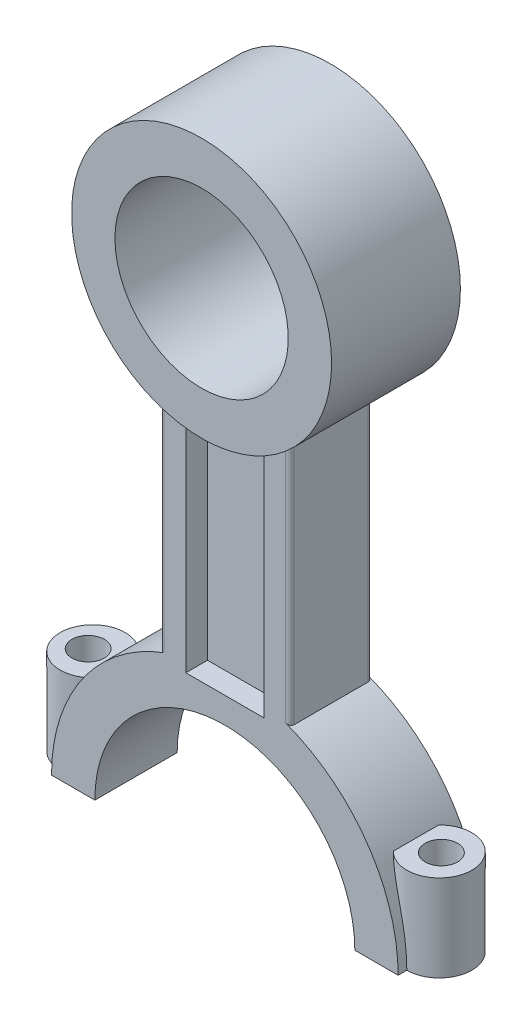
SolidWorks part; units mm, degrees
ref_plane "Front Plane" through (0, 0, 0) normal (0, 0, 1) x (1, 0, 0)
ref_plane "Top Plane" through (0, 0, 0) normal (0, 1, 0) x (1, 0, 0)
ref_plane "Right Plane" through (0, 0, 0) normal (1, 0, 0) x (0, 0, -1)
sketch "Sketch1" plane through (0, 0, 0) normal (0, 0, 1) x (1, 0, 0)
  line L0 (0, 76.2) -> (0, -76.2)
  line L2 (19.05, 59.3995) -> (19.05, -50.9435)
  line L3 (19.05, -50.9435) -> (-19.05, -50.9435)
  line L4 (-19.05, -50.9435) -> (-19.05, 59.3995)
  line L5 (-19.05, 59.3995) -> (19.05, 59.3995)
  line L6 (-50.8, -76.2) -> (-38.1, -76.2)
  line L7 (38.1, -76.2) -> (50.8, -76.2)
  circle A0 centre (0, 76.2) radius 25.4
  circle A1 centre (0, 76.2) radius 38.1
  arc A2 (50.8, -76.2) -> (-50.8, -76.2) centre (0, -76.2) ccw
  arc A3 (38.1, -76.2) -> (-38.1, -76.2) centre (0, -76.2) ccw
  dimension "D3" = 50.8
  dimension "D4" = 76.2
  dimension "D5" = 76.2
  dimension "D6" = 101.6
  dimension "D1" = 152.4
  dimension "D7" = 38.1
  dimension "D8" = 38.1
extrude "Boss-Extrude1" add sketch "Sketch1" along normal mid plane 24.13 contours A2 L0 A1 L4 | A2 L2 A1 L0 | A3 L4 A2 L6 | A3 L0 A2 L4 | A3 L7 A2 L2 | A3 L2 A2 L0 | L2 A1 L4 A0 | L4 A1 L0 A0 | L0 A1 L2 A0 region at (9.8942, 46.7377, 0) region at (-9.8942, 46.7377, 0) region at (-20.0922, 51.302, 0) region at (9.7333, 6.576, 0) region at (-9.7333, 6.576, 0) region at (9.6881, -33.2254, 0) region at (-9.6881, -33.2254, 0) region at (-35.8824, -53.4043, 0) region at (35.8824, -53.4043, 0)
extrude "Boss-Extrude2" add sketch "Sketch1<3>" along normal mid plane 37.75 contours L2 A1 L4 A0 | L4 A1 L0 A0 | L0 A1 L2 A0 region at (9.8942, 46.7377, 0) region at (-9.8942, 46.7377, 0) region at (-20.0922, 51.302, 0)
sketch "Sketch1<3>" plane through (0, 0, 0) normal (0, 0, 1) x (1, 0, 0) same geometry as "Sketch1"
sketch "Sketch4" plane through (0, -76.2, 0) normal (0, -1, 0) x (1, 0, 0)
  line L0 (50.8, 12.065) -> (50.8, -12.065) construction
  circle A0 centre (50.8, 0) radius 9.525
  dimension "D1" = 19.05
extrude "Boss-Extrude5" add sketch "Sketch4" against normal blind 25.4 contours A0
sketch "Sketch5" plane through (0, -76.2, 0) normal (0, -1, 0) x (1, 0, 0)
  circle A0 centre (51.3953, 0) radius 4.76
  dimension "D1" = 9.52
extrude "Cut-Extrude1" cut sketch "Sketch5" against normal blind 25.4
sketch "Sketch6" plane through (0, -76.2, 0) normal (0, -1, 0) x (1, 0, 0)
  line L0 (-50.8, 12.065) -> (-50.8, -12.065) construction
  circle A0 centre (-50.8, 0) radius 9.525
  dimension "D1" = 19.05
extrude "Boss-Extrude6" add sketch "Sketch6" against normal blind 25.4
sketch "Sketch7" plane through (0, -76.2, 0) normal (0, -1, 0) x (1, 0, 0)
  circle A0 centre (-52.1224, 0) radius 4.76
  dimension "D1" = 9.52
extrude "Cut-Extrude2" cut sketch "Sketch7" against normal blind 25.4
sketch "Sketch9" plane through (0, 0, 12.065) normal (0, 0, 1) x (1, 0, 0)
  line L1 (-11.43, 39.8549) -> (11.43, 39.8549) construction
  line L2 (11.43, 39.8549) -> (11.43, -30.5351)
  line L3 (11.43, -30.5351) -> (-11.43, -30.5351)
  line L5 (-11.43, 39.8549) -> (-11.43, -30.5351)
  line L6 (-11.43, 39.8549) -> (11.43, -30.5351) construction
  line L7 (11.43, 39.8549) -> (-11.43, -30.5351) construction
  circle A0 centre (0, 76.2) radius 38.1 construction
  point P0 (0, 0)
  arc M10 (19.05, 43.2044) -> (-19.05, 43.2044) centre (0, 76.2) cw
  dimension "D1" = 70.39
  dimension "D2" = 22.86
fillet "Fillet1" radius 1.25 1 edges at (19.05, 7.0486, 12.065)
fillet "Fillet2" radius 1.25 3 edges at (19.05, 7.0486, -12.065) (-19.05, 7.0486, -12.065) (-19.05, 7.0486, 12.065)
extrude "Cut-Extrude5" cut sketch "Sketch9" against normal blind 6.35 and the other way through all contours L5 L3 L2 M10 region at (0, 4.0742, 12.065)
mirror "Mirror1" about plane through (0, 0, 0) normal (0, 0, 1) of "Cut-Extrude5"
